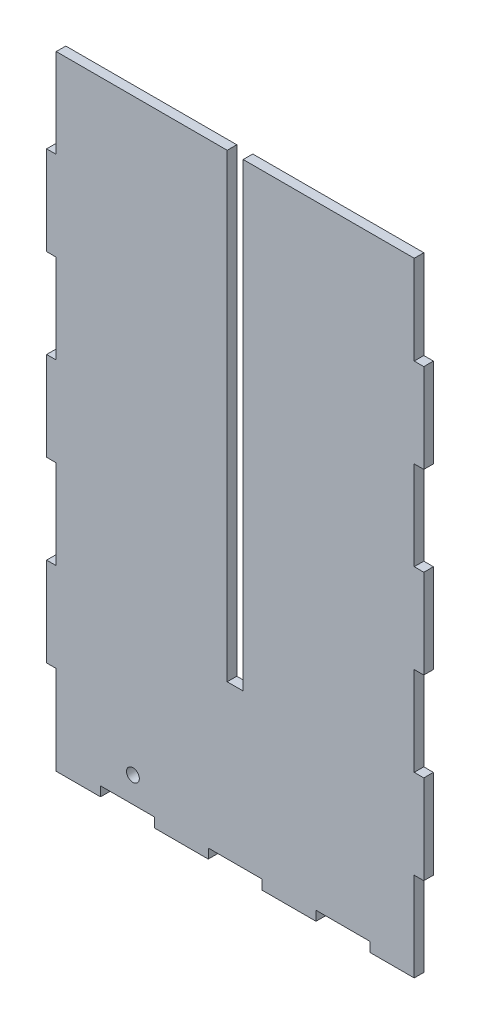
SolidWorks part; units mm, degrees
ref_plane "Front Plane" through (0, 0, 0) normal (0, 0, 1) x (1, 0, 0)
ref_plane "Top Plane" through (0, 0, 0) normal (0, 1, 0) x (1, 0, 0)
ref_plane "Right Plane" through (0, 0, 0) normal (1, 0, 0) x (0, 0, -1)
sketch "Sketch2" plane through (0, 0, 0) normal (0, 0, 1) x (1, 0, 0)
  line L0 (0, 152.4) -> (0, -152.4) construction
  line L1 (-88.9, 152.4) -> (88.9, 152.4)
  line L2 (-88.9, 152.4) -> (-88.9, -152.4)
  line L3 (-88.9, -152.4) -> (88.9, -152.4)
  line L4 (88.9, 152.4) -> (88.9, -152.4)
  line L5 (-88.9, 108.1768) -> (-88.9, 63.9536)
  line L6 (-88.9, 152.4) -> (-93.6625, 152.4)
  line L7 (-88.9, 152.4) -> (-88.9, 108.1768)
  line L8 (-88.9, 108.1768) -> (-93.6625, 108.1768)
  line L9 (-93.6625, 152.4) -> (-93.6625, 108.1768)
  line L10 (88.9, 152.4) -> (93.6625, 152.4)
  line L11 (88.9, 152.4) -> (88.9, 108.1768)
  line L12 (88.9, 108.1768) -> (93.6625, 108.1768)
  line L13 (93.6625, 152.4) -> (93.6625, 108.1768)
  line L14 (-66.9018, -152.4) -> (-93.6625, -152.4)
  line L15 (-66.9018, -152.4) -> (-66.9018, -157.1625)
  line L16 (-66.9018, -157.1625) -> (-93.6625, -157.1625)
  line L17 (-93.6625, -152.4) -> (-93.6625, -157.1625)
  line L18 (-88.9, 108.1768) -> (-93.6625, 108.1768)
  line L19 (-93.6625, 108.1768) -> (-93.6625, 63.9536)
  line L20 (-88.9, 63.9536) -> (-93.6625, 63.9536)
  line L21 (88.9, 108.1768) -> (88.9, 63.9536)
  line L22 (88.9, 108.1768) -> (93.6625, 108.1768)
  line L23 (93.6625, 108.1768) -> (93.6625, 63.9536)
  line L24 (88.9, 63.9536) -> (93.6625, 63.9536)
  line L25 (-88.9, 63.9536) -> (-88.9, 19.7304)
  line L26 (-88.9, 63.9536) -> (-93.6625, 63.9536)
  line L27 (-93.6625, 63.9536) -> (-93.6625, 19.7304)
  line L28 (-88.9, 19.7304) -> (-93.6625, 19.7304)
  line L29 (88.9, 63.9536) -> (88.9, 19.7304)
  line L30 (88.9, 63.9536) -> (93.6625, 63.9536)
  line L31 (93.6625, 63.9536) -> (93.6625, 19.7304)
  line L32 (88.9, 19.7304) -> (93.6625, 19.7304)
  line L33 (-88.9, 19.7304) -> (-88.9, -24.4929)
  line L34 (-88.9, 19.7304) -> (-93.6625, 19.7304)
  line L35 (-93.6625, 19.7304) -> (-93.6625, -24.4929)
  line L36 (-88.9, -24.4929) -> (-93.6625, -24.4929)
  line L37 (88.9, 19.7304) -> (88.9, -24.4929)
  line L38 (88.9, 19.7304) -> (93.6625, 19.7304)
  line L39 (93.6625, 19.7304) -> (93.6625, -24.4929)
  line L40 (88.9, -24.4929) -> (93.6625, -24.4929)
  line L41 (-88.9, -24.4929) -> (-88.9, -68.7161)
  line L42 (-88.9, -24.4929) -> (-93.6625, -24.4929)
  line L43 (-93.6625, -24.4929) -> (-93.6625, -68.7161)
  line L44 (-88.9, -68.7161) -> (-93.6625, -68.7161)
  line L45 (88.9, -24.4929) -> (88.9, -68.7161)
  line L46 (88.9, -24.4929) -> (93.6625, -24.4929)
  line L47 (93.6625, -24.4929) -> (93.6625, -68.7161)
  line L48 (88.9, -68.7161) -> (93.6625, -68.7161)
  line L49 (-88.9, -68.7161) -> (-88.9, -112.9393)
  line L50 (-88.9, -68.7161) -> (-93.6625, -68.7161)
  line L51 (-93.6625, -68.7161) -> (-93.6625, -112.9393)
  line L52 (-88.9, -112.9393) -> (-93.6625, -112.9393)
  line L53 (88.9, -68.7161) -> (88.9, -112.9393)
  line L54 (88.9, -68.7161) -> (93.6625, -68.7161)
  line L55 (93.6625, -68.7161) -> (93.6625, -112.9393)
  line L56 (88.9, -112.9393) -> (93.6625, -112.9393)
  line L57 (-88.9, -112.9393) -> (-88.9, -157.1625)
  line L58 (-88.9, -112.9393) -> (-93.6625, -112.9393)
  line L59 (-93.6625, -112.9393) -> (-93.6625, -157.1625)
  line L60 (-88.9, -157.1625) -> (-93.6625, -157.1625)
  line L61 (88.9, -112.9393) -> (88.9, -157.1625)
  line L62 (88.9, -112.9393) -> (93.6625, -112.9393)
  line L63 (93.6625, -112.9393) -> (93.6625, -157.1625)
  line L64 (88.9, -157.1625) -> (93.6625, -157.1625)
  line L65 (-40.1411, -152.4) -> (-40.1411, -157.1625)
  line L66 (-40.1411, -152.4) -> (-66.9018, -152.4)
  line L67 (-66.9018, -152.4) -> (-66.9018, -157.1625)
  line L68 (-40.1411, -157.1625) -> (-66.9018, -157.1625)
  line L69 (-13.3804, -152.4) -> (-13.3804, -157.1625)
  line L70 (-13.3804, -152.4) -> (-40.1411, -152.4)
  line L71 (-40.1411, -152.4) -> (-40.1411, -157.1625)
  line L72 (-13.3804, -157.1625) -> (-40.1411, -157.1625)
  line L73 (13.3804, -152.4) -> (13.3804, -157.1625)
  line L74 (13.3804, -152.4) -> (-13.3804, -152.4)
  line L75 (-13.3804, -152.4) -> (-13.3804, -157.1625)
  line L76 (13.3804, -157.1625) -> (-13.3804, -157.1625)
  line L77 (40.1411, -152.4) -> (40.1411, -157.1625)
  line L78 (40.1411, -152.4) -> (13.3804, -152.4)
  line L79 (13.3804, -152.4) -> (13.3804, -157.1625)
  line L80 (40.1411, -157.1625) -> (13.3804, -157.1625)
  line L81 (66.9018, -152.4) -> (66.9018, -157.1625)
  line L82 (66.9018, -152.4) -> (40.1411, -152.4)
  line L83 (40.1411, -152.4) -> (40.1411, -157.1625)
  line L84 (66.9018, -157.1625) -> (40.1411, -157.1625)
  line L85 (93.6625, -152.4) -> (93.6625, -157.1625)
  line L86 (93.6625, -152.4) -> (66.9018, -152.4)
  line L87 (66.9018, -152.4) -> (66.9018, -157.1625)
  line L88 (93.6625, -157.1625) -> (66.9018, -157.1625)
  point P6 (0, 0)
  dimension "D1" = 177.8
  dimension "D2" = 187.325
  dimension "D3" = 304.8
  dimension "D4" = 309.5625
  dimension "D6" = 44.2232
  dimension "D8" = 26.7607
  dimension "D5" = 7
  dimension "D7" = 7
extrude "Boss-Extrude1" add sketch "Sketch2" along normal blind 4.7625 contours L0 L1 L2 L3 | L1 L0 L3 L4 | L20 L2 L8 L19 | L36 L2 L28 L35 | L52 L2 L44 L51 | L3 L57 L16 L15 | L72 L69 L3 L65 | L80 L77 L3 L73 | L4 L56 L55 L48 | L4 L40 L39 L32 | L4 L24 L23 L12 | L88 L61 L3 L81 region at (44.45, 0, 0) region at (-44.45, 0, 0) region at (-26.7607, -154.7812, 0) region at (26.7607, -154.7813, 0) region at (-91.2812, 86.0652, 0) region at (91.2813, 86.0652, 0) region at (-77.9009, -154.7813, 0) region at (77.9009, -154.7813, 0) region at (-91.2812, -2.3813, 0) region at (91.2813, -2.3813, 0) region at (-91.2812, -90.8277, 0) region at (91.2813, -90.8277, 0)
sketch "Sketch3" plane through (0, 0, 4.7625) normal (0, 0, 1) x (1, 0, 0)
  line L0 (-88.9, 152.4) -> (88.9, 152.4) construction
  line L1 (-3.9688, 152.4) -> (3.9687, 152.4)
  line L2 (-3.9688, 152.4) -> (-3.9687, -76.2)
  line L3 (-3.9687, -76.2) -> (3.9688, -76.2)
  line L4 (3.9687, 152.4) -> (3.9688, -76.2)
  line L5 (0, -76.2) -> (0, 0) construction
  dimension "D1" = 7.9375
  dimension "D2" = 228.6
extrude "Cut-Extrude1" cut sketch "Sketch3" against normal through all
sketch "Sketch4" plane through (0, 0, 4.7625) normal (0, 0, 1) x (1, 0, 0)
  line L0 (-66.9018, -152.4) -> (-40.1411, -152.4) construction
  line L1 (-88.9, -112.9393) -> (-88.9, -157.1625) construction
  circle A0 centre (-50.8, -139.7) radius 3.175
  dimension "D1" = 6.35
  dimension "D2" = 12.7
  dimension "D3" = 38.1
extrude "Cut-Extrude2" cut sketch "Sketch4" against normal through all
equation "\"Height\"= 12in"
equation "\"Depth\"= 7in"
equation "\"WallThickness\"= 0.1875in"
equation "\"FloorThickness\"= 0.1875in"
equation "\"D1@Sketch2\"=\"Depth\""
equation "\"D2@Sketch2\"=\"D1@Sketch2\"+2*\"WallThickness\""
equation "\"D3@Sketch2\"=\"Height\""
equation "\"D4@Sketch2\"=\"D3@Sketch2\"+\"WallThickness\""
equation "\"D6@Sketch2\"=\"D4@Sketch2\"/\"D5@Sketch2\""
equation "\"D8@Sketch2\"=\"D2@Sketch2\"/\"D7@Sketch2\""
equation "\"D1@Boss-Extrude1\"=\"WallThickness\""
equation "\"Width\"= 30in"
